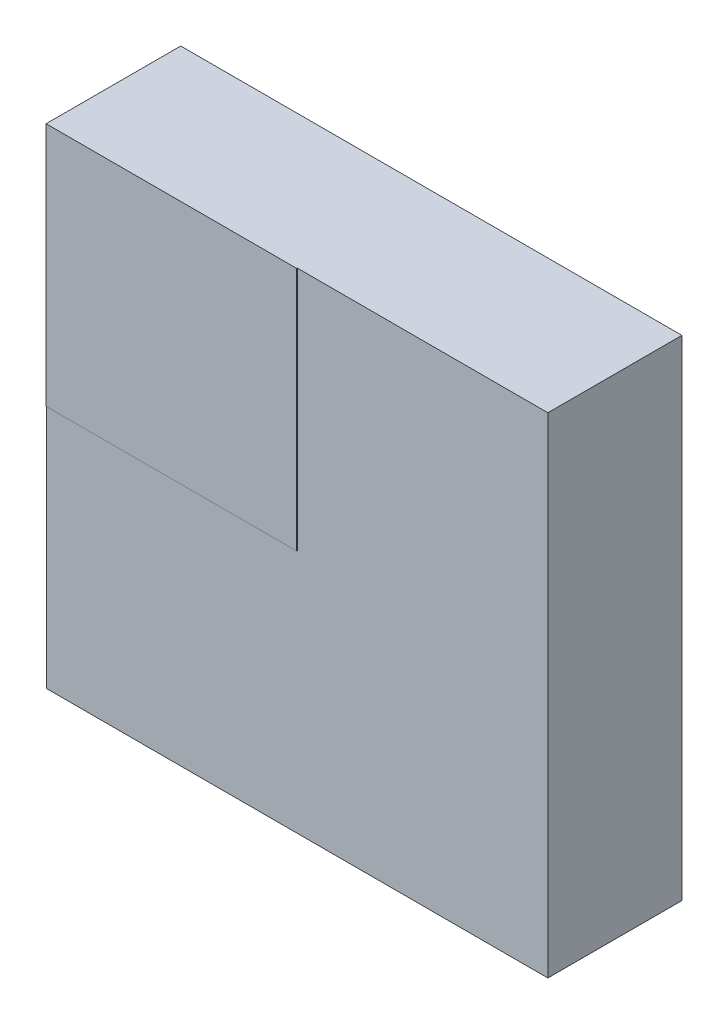
SolidWorks part; units mm, degrees
ref_plane "Front Plane" through (0, 0, 0) normal (0, 0, 1) x (1, 0, 0)
ref_plane "Top Plane" through (0, 0, 0) normal (0, 1, 0) x (1, 0, 0)
ref_plane "Right Plane" through (0, 0, 0) normal (1, 0, 0) x (0, 0, -1)
sketch "Sketch1" plane through (0, 0, 0) normal (0, 0, 1) x (1, 0, 0)
  line L1 (-0.43, -0.42) -> (0.43, -0.42)
  line L2 (-0.43, -0.42) -> (-0.43, 0.42)
  line L3 (-0.43, 0.42) -> (0.43, 0.42)
  line L4 (0.43, -0.42) -> (0.43, 0.42)
  line L5 (-0.43, -0.42) -> (0.43, 0.42) construction
  line L6 (-0.43, 0.42) -> (0.43, -0.42) construction
  point P0 (0, 0)
  dimension "D1" = 0.86
  dimension "D2" = 0.84
extrude "Boss-Extrude1" add sketch "Sketch1" along normal blind 0.23
sketch "Sketch2" plane through (0, 0, 0.23) normal (0, 0, 1) x (1, 0, 0)
  line L1 (-0.43, 0.42) -> (0, 0.42)
  line L2 (-0.43, 0.42) -> (-0.43, 0)
  line L3 (-0.43, 0) -> (0, 0)
  line L4 (0, 0.42) -> (0, 0)
  point P6 (-0.32, 0.32)
  point P7 (-0.3819, 0.3819)
  point P8 (-0.43, 0.42)
extrude "Boss-Extrude2" add sketch "Sketch2" along normal blind 0.001
sketch "Sketch3" plane through (0, 0, 0) normal (0, 0, -1) x (-1, 0, 0)
  circle A1 centre (-0.2, 0.2) radius 0.09
  dimension "D3" = 0.18
  dimension "D1" = 0.2
  dimension "D2" = 0.2
extrude "Boss-Extrude3" add sketch "Sketch3" along normal blind 0.1 contours A1
fillet "Fillet1" radius 0.09 1 edges at (0.11, 0.2, -0.1) conic rho 0.5
pattern_linear "LPattern2" count 2 spacing 0.4 along (-1, 0, 0) count 2 spacing 0.4 along (0, -1, 0) of "Fillet1", "Boss-Extrude3"
